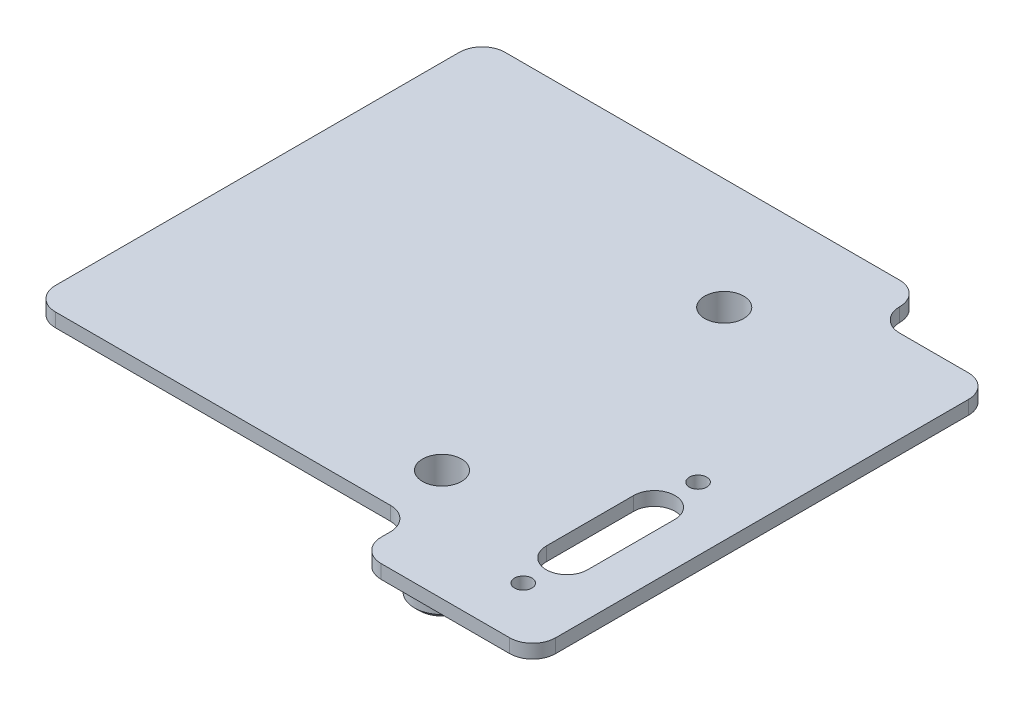
SolidWorks part; units mm, degrees
ref_plane "Front Plane" through (0, 0, 0) normal (0, 0, 1) x (1, 0, 0)
ref_plane "Top Plane" through (0, 0, 0) normal (0, 1, 0) x (1, 0, 0)
ref_plane "Right Plane" through (0, 0, 0) normal (1, 0, 0) x (0, 0, -1)
sketch "Sketch1" plane through (0, 0, 0) normal (0, 1, 0) x (1, 0, 0)
  line L0 (0, 0) -> (83, 0)
  line L1 (83, 0) -> (83, -12)
  line L2 (83, -12) -> (121, -12)
  line L3 (121, -12) -> (121, 88)
  line L5 (0, 98) -> (0, 0)
  line L6 (0, 43) -> (121, 43) construction
  line L7 (77, 73.75) -> (77, 12.25) construction
  line L8 (0, 98) -> (96, 98)
  line L9 (96, 98) -> (96, 88)
  line L10 (96, 88) -> (121, 88)
  line L11 (86.8502, -12) -> (86.8502, 98) construction
  point P11 (77, 43)
  point P13 (77, 73.75)
  point P14 (77, 12.25)
  point P18 (86.8502, 43)
  dimension "D1" = 121
  dimension "D2" = 110
  dimension "D3" = 38
  dimension "D4" = 12
  dimension "D5" = 61.5
  dimension "D6" = 44
  dimension "D7" = 10
  dimension "D8" = 25
extrude "plate" add sketch "Sketch1" along normal blind 3
sketch "Sketch2" plane through (0, 0, 0) normal (0, 1, 0) x (1, 0, 0)
  circle A0 centre (77, 73.75) radius 6
  circle A1 centre (77, 12.25) radius 6
  dimension "D1" = 12
extrude "mount posts" add sketch "Sketch2" against normal blind 21
sketch "Sketch3" plane through (0, 3, 0) normal (0, 1, 0) x (1, 0, 0)
  circle A0 centre (77, 73.75) radius 4.25
  circle A1 centre (77, 12.25) radius 4.25
  dimension "D1" = 8.5
extrude "mount cbore" cut sketch "Sketch3" against normal offset from surface (20 mm away) 4 up to face at (77, -21, -67.75)
hole_wizard "#8 Clearance Hole1" positions "Sketch4" profile "Sketch5" hole size "#8" standard "ANSI Inch" end condition through all
sketch "Sketch4" plane through (0, -17, 0) normal (0, 1, 0) x (1, 0, 0)
  circle A0 centre (77, 12.25) radius 4.25 construction
  circle A1 centre (77, 73.75) radius 4.25 construction
  point P0 (77, 73.75)
  point P2 (77, 12.25)
sketch "Sketch5" plane through (77, -17, -73.75) normal (1, 0, 0) x (0, 0, 1)
  line L0 (0, 0) -> (0, 4)
  line L1 (0, 4) -> (2.2479, 4)
  line L2 (2.2479, 4) -> (2.2479, 0)
  line L5 (2.2479, 0) -> (0, 0)
  line L11 (0, -6.35) -> (0, 107.95) construction
  dimension "Thru Hole Dia." = 4.4958
  dimension "Thru Hole Depth" = 4
ref_plane "mid plane" through (0, 0, -43) normal (0, 0, -1) x (1, 0, 0)
sketch "Sketch8" plane through (0, 0, -43) normal (0, 0, -1) x (1, 0, 0)
  line L0 (47.25, 0) -> (48.85, 0)
  line L1 (0, 0) -> (121, 0) construction
  line L2 (47.25, 0) -> (45.5, 29)
  line L3 (45.5, 29) -> (47.1, 29)
  line L4 (47.1, 29) -> (48.85, 0)
  line L5 (42, 0) -> (42, 41.9178) construction
  line L6 (81.4832, 21) -> (59.4094, 21) construction
  line L8 (83, 21) -> (71, 21) construction
  dimension "D1" = 1.6
  dimension "D2" = 3.5
  dimension "D3" = 8
  dimension "D4" = 5.25
  dimension "D5" = 42
revolve "foot" add sketch "Sketch8" angle 360 about L5
fillet "Fillet1" radius 1.5 2 edges at (42, 0, -37.75) (42, 0, -36.15)
sketch "Sketch7" plane through (0, 3, 0) normal (0, 1, 0) x (1, 0, 0)
  line L0 (107.15, 87.7375) -> (107.15, 106.2625) construction
  line L1 (121, -12) -> (121, 88) construction
  line L2 (83, -12) -> (121, -12) construction
  line L3 (115, 18.85) -> (99.3, 18.85) construction
  line L4 (102.65, 9.325) -> (102.65, 28.375)
  line L5 (99.3, -6) -> (99.3, 43.7) construction
  line L6 (99.3, -6) -> (115, -6) construction
  line L7 (115, -6) -> (115, 43.7) construction
  line L8 (99.3, 43.7) -> (115, 43.7) construction
  line L9 (99.3, -6) -> (115, 43.7) construction
  line L10 (115, -6) -> (99.3, 43.7) construction
  line L11 (111.65, 9.325) -> (111.65, 28.375)
  circle A0 centre (107.15, 9.325) radius 4.5 construction
  circle A1 centre (107.15, 28.375) radius 4.5 construction
  arc A2 (102.65, 9.325) -> (111.65, 9.325) centre (107.15, 9.325) ccw
  arc A3 (102.65, 28.375) -> (111.65, 28.375) centre (107.15, 28.375) cw
  circle A4 centre (107.15, 37.9) radius 1.9
  circle A5 centre (107.15, -0.2) radius 1.9
  point P16 (107.15, 18.85)
  point P19 (102, -12)
  dimension "D2" = 19.05
  dimension "D5" = 9
  dimension "D6" = 3.8
  dimension "D1" = 49.7
  dimension "D3" = 6
  dimension "D4" = 15.7
  dimension "D7" = 38.1
  dimension "D8" = 6
extrude "terminal strip" cut sketch "Sketch7" against normal through all
chamfer "Chamfer1" distance 3 angle 45 2 edges at (77, -17, -69.5) (77, -17, -8)
chamfer "Chamfer2" distance 1 angle 45 2 edges at (77, -21, -6.25) (77, -21, -67.75)
fillet "Fillet3" radius 1.5 2 edges at (77, 0, -67.75) (77, 0, -6.25)
fillet "corners" radius 5 8 edges at (0, 1.5, -98) (96, 1.5, -98) (96, 1.5, -88) (121, 1.5, -88) (121, 1.5, 12) (83, 1.5, 12) (83, 1.5, 0) (0, 1.5, 0)
